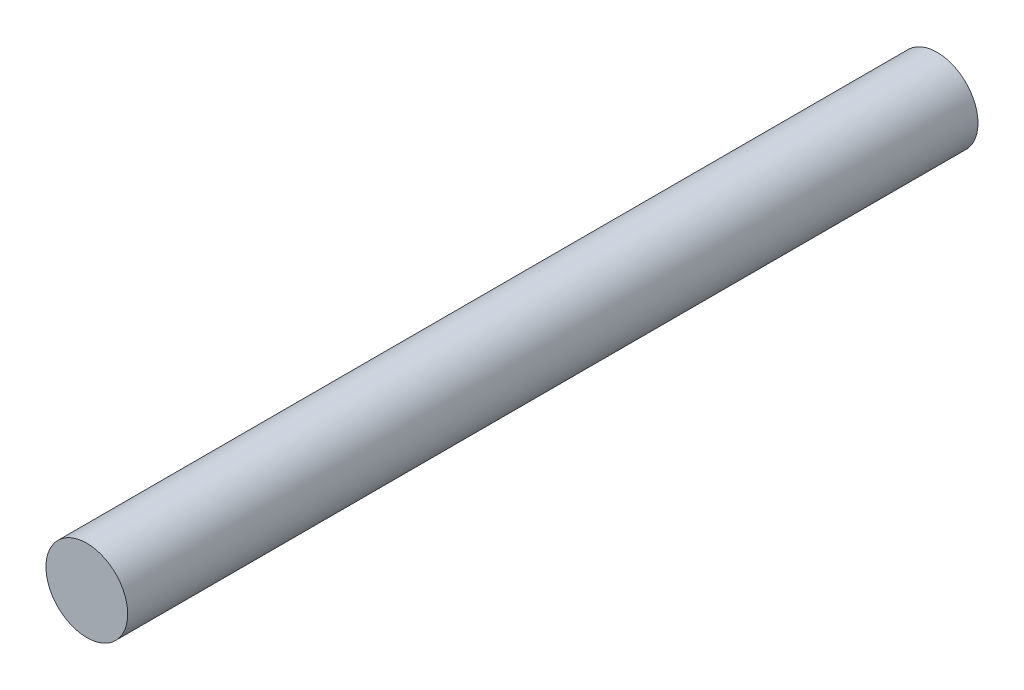
SolidWorks part; units mm, degrees
ref_plane "Front Plane" through (0, 0, 0) normal (0, 0, 1) x (1, 0, 0)
ref_plane "Top Plane" through (0, 0, 0) normal (0, 1, 0) x (1, 0, 0)
ref_plane "Right Plane" through (0, 0, 0) normal (1, 0, 0) x (0, 0, -1)
sketch "Sketch1" plane through (0, 0, 0) normal (0, 0, 1) x (1, 0, 0)
  circle A0 centre (0, 0) radius 15.875
  dimension "D1" = 31.75
extrude "Boss-Extrude1" add sketch "Sketch1" along normal blind 330.2
sketch "Sketch2" plane through (0, 0, 330.2) normal (0, 0, 1) x (1, 0, 0)
  point P0 (0, 0)
sketch "Sketch3" plane through (0, 0, 0) normal (0, 0, -1) x (-1, 0, 0)
  point P0 (0, 0)
ref_axis "Axis1" through (0, 0, 330.2) along (0, 0, -1)
